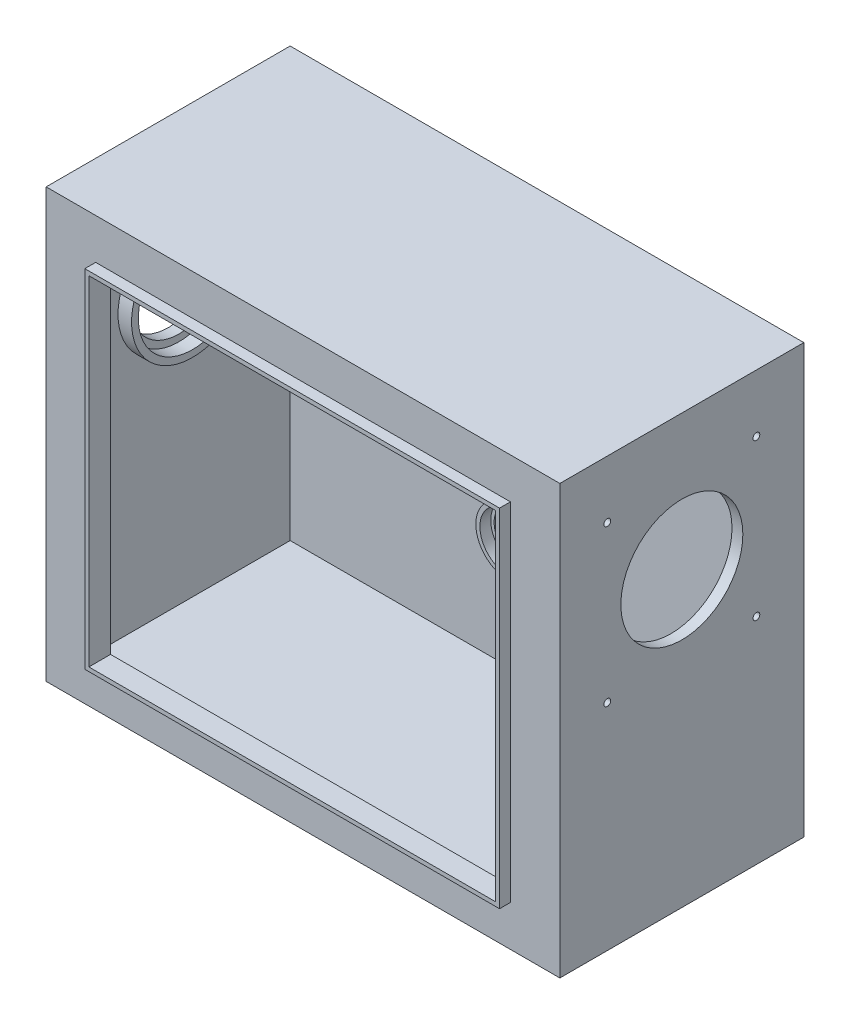
SolidWorks part; units mm, degrees
ref_plane "Alzado" through (0, 0, 0) normal (0, 0, 1) x (1, 0, 0)
ref_plane "Planta" through (0, 0, 0) normal (0, 1, 0) x (1, 0, 0)
ref_plane "Vista lateral" through (0, 0, 0) normal (1, 0, 0) x (0, 0, -1)
sketch "Croquis1" plane through (0, 0, 0) normal (0, 0, 1) x (1, 0, 0)
  line L0 (-189.5, 158) -> (189.5, 158)
  line L1 (-181.5, -150) -> (181.5, -150) construction
  line L2 (-181.5, -150) -> (-181.5, 150) construction
  line L3 (-181.5, 150) -> (181.5, 150) construction
  line L4 (181.5, -150) -> (181.5, 150) construction
  line L5 (-181.5, -150) -> (181.5, 150) construction
  line L6 (-181.5, 150) -> (181.5, -150) construction
  line L7 (189.5, -158) -> (189.5, 158)
  line L8 (-189.5, -158) -> (189.5, -158)
  line L9 (-189.5, -158) -> (-189.5, 158)
  point P0 (0, 0)
  dimension "D1" = 363
  dimension "D2" = 300
  dimension "D3" = 8
extrude "Saliente-Extruir1" add sketch "Croquis1" along normal blind 180
shell "Vaciado1" thickness 8 removed face at (0, 0, 180)
sketch "Croquis2" plane through (-189.5, 0, 0) normal (-1, 0, 0) x (0, 0, 1)
  line L0 (0, 158) -> (90, 158) construction
  line L1 (180, 158) -> (0, 158) construction
  circle A0 centre (90, 58) radius 35
extrude "Cortar-Extruir4" cut sketch "Croquis2" against normal blind 20 contours A0
sketch "Croquis4" plane through (-181.5, 0, 0) normal (1, 0, 0) x (0, 0, -1)
  circle A1 centre (-90, 58) radius 40
  circle A2 centre (-90, 58) radius 45
extrude "Saliente-Extruir4" add sketch "Croquis4" along normal blind 10
sketch "Croquis6" plane through (189.5, 0, 0) normal (1, 0, 0) x (0, 0, -1)
  line L0 (-90, 158) -> (-90, 58) construction
  line L1 (-180, 158) -> (0, 158) construction
  circle A0 centre (-90, 58) radius 45
  dimension "D1" = 90
extrude "Cortar-Extruir6" cut sketch "Croquis6" against normal blind 10 contours A0
sketch "Croquis7" plane through (0, 0, 8) normal (0, 0, 1) x (1, 0, 0)
  circle A3 centre (-2.5, -53) radius 21
  circle A4 centre (-2.5, -53) radius 24
  dimension "D1" = 42
  dimension "D2" = 48
extrude "Saliente-Extruir9" add sketch "Croquis7" along normal blind 18
ref_plane "Plano6" through (0, 0, 180) normal (0, 0, 1) x (1, 0, 0)
sketch "Croquis11" plane through (0, 0, 180) normal (0, 0, 1) x (1, 0, 0)
  line L1 (181.5, 150) -> (-181.5, 150)
  line L2 (181.5, 150) -> (181.5, -150)
  line L3 (181.5, -150) -> (-181.5, -150)
  line L4 (-181.5, 150) -> (-181.5, -150)
  line L5 (181.5, 150) -> (-181.5, -150) construction
  line L6 (181.5, -150) -> (-181.5, 150) construction
  line L7 (-150, 125) -> (150, 125)
  line L8 (-150, 125) -> (-150, -125)
  line L9 (-150, -125) -> (150, -125)
  line L10 (150, 125) -> (150, -125)
  line L11 (-150, 125) -> (150, -125) construction
  line L12 (-150, -125) -> (150, 125) construction
  point P0 (0, 0)
  point P7 (0, 0)
  dimension "D1" = 300
  dimension "D2" = 250
extrude "Saliente-Extruir10" add sketch "Croquis11" against normal blind 8
sketch "Croquis12" plane through (0, 0, 180) normal (0, 0, 1) x (1, 0, 0)
  line L1 (150, -125) -> (-150, -125)
  line L2 (150, -125) -> (150, 125)
  line L3 (150, 125) -> (-150, 125)
  line L4 (-150, -125) -> (-150, 125)
  line L5 (150, -125) -> (-150, 125) construction
  line L6 (150, 125) -> (-150, -125) construction
  line L7 (153, -128) -> (-153, -128)
  line L8 (153, -128) -> (153, 128)
  line L9 (153, 128) -> (-153, 128)
  line L10 (-153, -128) -> (-153, 128)
  line L11 (153, -128) -> (-153, 128) construction
  line L12 (153, 128) -> (-153, -128) construction
  point P0 (0, 0)
  point P8 (0, 0)
  dimension "D1" = 3
  dimension "D2" = 3
extrude "Saliente-Extruir11" add sketch "Croquis12" along normal blind 8
sketch "Croquis20" plane through (0, 0, 8) normal (0, 0, 1) x (1, 0, 0)
  circle A0 centre (-2.5, -53) radius 18.5
  circle A1 centre (-2.5, -53) radius 21
  circle A2 centre (-2.5, -53) radius 21 construction
  dimension "D1" = 37
extrude "Saliente-Extruir19" add sketch "Croquis20" along normal blind 10
hole_wizard "Taladro roscado M63" positions "Croquis3D6" profile "Croquis26" tap size "M6" standard "DIN" end condition through all
sketch3d "Croquis3D6"
  line L2 (-189.5, 0.5, 145) -> (-189.5, 115.5, 145) construction
  line L3 (-189.5, 0.5, 145) -> (-189.5, 0.5, 35) construction
  line L4 (-189.5, 0.5, 35) -> (-189.5, 115.5, 35) construction
  line L5 (-189.5, 115.5, 145) -> (-189.5, 115.5, 35) construction
  line L6 (-189.5, 0.5, 145) -> (-189.5, 115.5, 35) construction
  line L7 (-189.5, 0.5, 35) -> (-189.5, 115.5, 145) construction
  circle A1 centre (-189.5, 58, 90) radius 35 construction
  point P0 (-189.5, 115.5, 35)
  point P2 (-189.5, 115.5, 145)
  point P4 (-189.5, 0.5, 145)
  point P6 (-189.5, 0.5, 35)
  point P265 (-189.5, 58, 90)
  point P268 (-224.5, 58, 90)
  dimension "D1" = 115
  dimension "D2" = 0
  dimension "D3" = 110
sketch "Croquis26" plane through (-189.5, 115.5, 35) normal (0, 1, 0) x (0, 0, 1)
  line L0 (0, 0) -> (0, 379)
  line L1 (0, 379) -> (2.5, 379)
  line L2 (2.5, 379) -> (2.5, 0)
  line L5 (2.5, 0) -> (0, 0)
  line L11 (0, -6.35) -> (0, 107.95) construction
  dimension "Diámetro de perforador para roscar hasta el siguiente" = 5
  dimension "Profundidad de perforador para roscar hasta el siguiente" = 379
cosmetic thread "Rosca de taladro1" parameters "D2"=6
cosmetic thread "Rosca de taladro2" parameters "D2"=6
cosmetic thread "Rosca de taladro3" parameters "D2"=6
cosmetic thread "Rosca de taladro4" parameters "D2"=6
sketch "Croquis27" plane through (0, 0, 0) normal (0, 0, -1) x (-1, 0, 0)
  circle A0 centre (2.5, -53) radius 11
  circle A1 centre (2.5, -53) radius 21 construction
  dimension "D1" = 22
extrude "Cortar-Extruir7" cut sketch "Croquis27" against normal up to surface (8 mm away) up to face at (-26.5, -53, 8)
